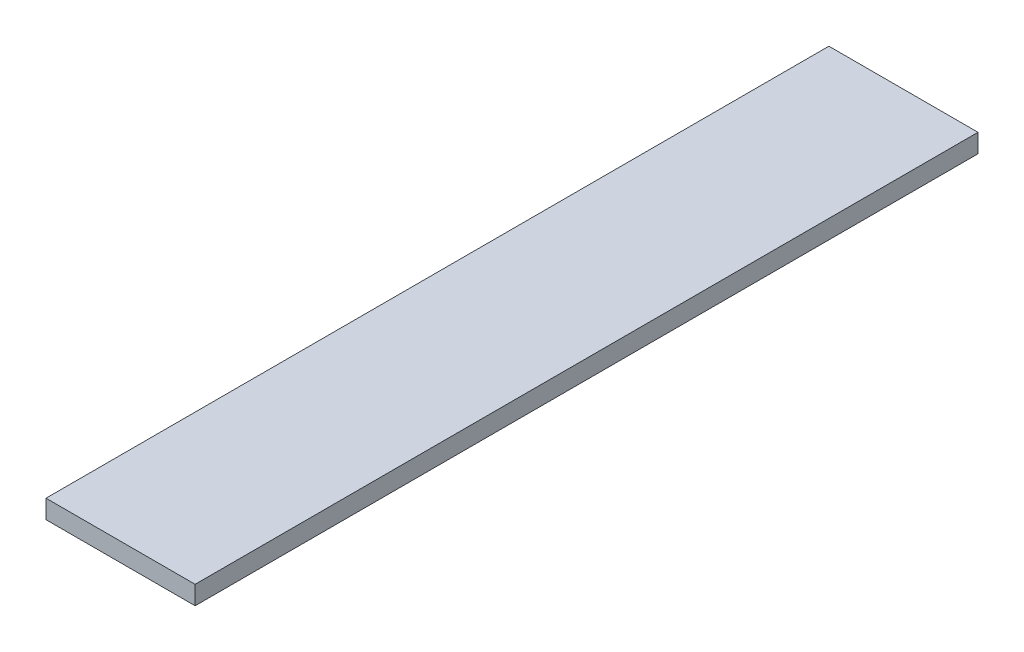
SolidWorks part; units mm, degrees
ref_plane "Front Plane" through (0, 0, 0) normal (0, 0, 1) x (1, 0, 0)
ref_plane "Top Plane" through (0, 0, 0) normal (0, 1, 0) x (1, 0, 0)
ref_plane "Right Plane" through (0, 0, 0) normal (1, 0, 0) x (0, 0, -1)
sketch "Sketch1" plane through (0, 0, 0) normal (0, 0, 1) x (1, 0, 0)
  line L0 (0, 1.5875) -> (0, -1.5875)
  line L1 (-12.7, 0) -> (12.7, 0) construction
  point P6 (0, 0)
  dimension "Width" = 25.4
  dimension "Thk" = 3.175
sketch "Sketch2" plane through (0, 0, 0) normal (1, 0, 0) x (0, 0, -1)
  line L0 (66.675, 0) -> (-66.675, 0)
  point P4 (0, 0)
  dimension "Length" = 133.35
sketch "Sketch3" plane through (0, 0, 0) normal (0, 0, 1) x (1, 0, 0)
  line L1 (12.7, 1.5875) -> (-12.7, 1.5875)
  line L2 (12.7, 1.5875) -> (12.7, -1.5875)
  line L3 (12.7, -1.5875) -> (-12.7, -1.5875)
  line L4 (-12.7, 1.5875) -> (-12.7, -1.5875)
  line L5 (12.7, 1.5875) -> (-12.7, -1.5875) construction
  line L6 (12.7, -1.5875) -> (-12.7, 1.5875) construction
  point P0 (0, 0)
extrude "Boss-Extrude1" add sketch "Sketch3" along normal up to vertex (66.675 mm away) and the other way up to vertex (66.675 mm away) up to point (0, 0, 66.675) other way up to point (0, 0, -66.675)
